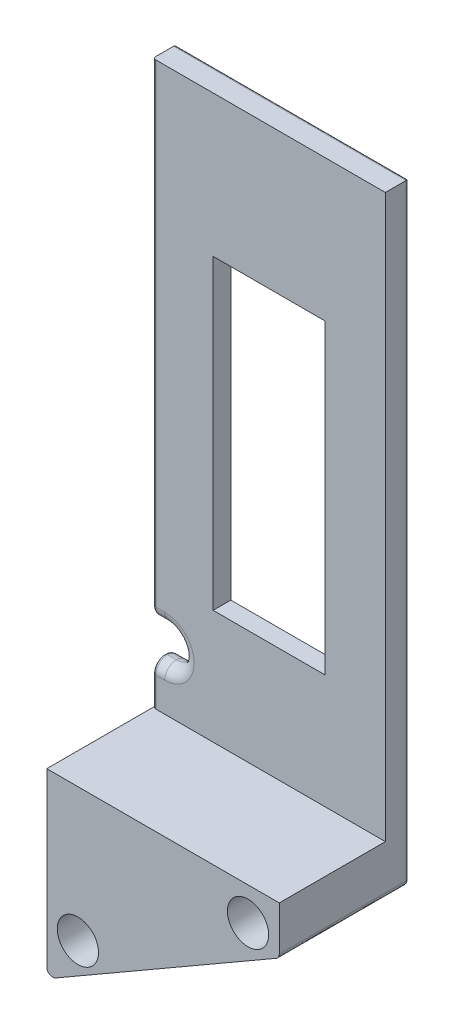
SolidWorks part; units mm, degrees
ref_plane "Front Plane" through (0, 0, 0) normal (0, 0, 1) x (1, 0, 0)
ref_plane "Top Plane" through (0, 0, 0) normal (0, 1, 0) x (1, 0, 0)
ref_plane "Right Plane" through (0, 0, 0) normal (1, 0, 0) x (0, 0, -1)
sketch "Model" plane through (0, 0, 0) normal (0, 0, 1) x (1, 0, 0)
  line L0 (-21.8431, 7.4481) -> (-8.6148, 30.3792)
  line L1 (-38.0636, 15.3297) -> (-23.771, 7.0696)
  line L2 (-75.3888, 20.2293) -> (-38.7189, 15.4592)
  line L3 (-86.2854, 34.8343) -> (-75.7419, 20.3766)
  line L4 (-29.1405, 92.9799) -> (-29.1405, 91.7303)
  line L5 (-8.8891, 91.2299) -> (-28.6402, 91.2299)
  line L6 (-8.3888, 90.7295) -> (-8.3888, 31.2555)
  line L7 (-86.6385, 34.9791) -> (-141.6396, 34.9791)
  line L8 (-142.1399, 90.7295) -> (-142.1399, 35.4795)
  line L9 (-104.6394, 91.2299) -> (-141.6396, 91.2299)
  line L10 (-104.139, 95.4793) -> (-104.139, 91.7303)
  line L11 (-85.6402, 95.9797) -> (-103.6387, 95.9797)
  line L12 (-85.1399, 97.7297) -> (-85.1399, 96.4801)
  line L13 (-67.6393, 98.2301) -> (-84.6395, 98.2301)
  line L14 (-67.1389, 96.4801) -> (-67.1389, 97.7297)
  line L15 (-48.6401, 95.9797) -> (-66.6385, 95.9797)
  line L16 (-48.1397, 93.9807) -> (-48.1397, 95.4793)
  line L17 (-29.6384, 93.4803) -> (-47.6393, 93.4803)
  line L18 (135.1563, 30.6526) -> (116.2359, 41.5721)
  line L19 (123.1828, 7.2669) -> (135.5373, 28.7222)
  line L20 (106.9623, 15.1485) -> (121.2549, 6.8884)
  line L21 (69.6371, 20.0481) -> (106.307, 15.278)
  line L22 (58.7405, 34.6531) -> (69.284, 20.1955)
  line L23 (115.8854, 92.7987) -> (115.8828, 42.2376)
  line L24 (58.3874, 34.7979) -> (3.3863, 34.7979)
  line L25 (2.886, 90.5483) -> (2.886, 35.2983)
  line L26 (40.3865, 91.0487) -> (3.3863, 91.0487)
  line L27 (40.8869, 95.2981) -> (40.8869, 91.5491)
  line L28 (59.3857, 95.7985) -> (41.3872, 95.7985)
  line L29 (59.886, 97.5485) -> (59.886, 96.2989)
  line L30 (77.3866, 98.0489) -> (60.3864, 98.0489)
  line L31 (77.887, 96.2989) -> (77.887, 97.5485)
  line L32 (96.3858, 95.7985) -> (78.3874, 95.7985)
  line L33 (96.8862, 93.7995) -> (96.8862, 95.2981)
  line L34 (115.3875, 93.2991) -> (97.3866, 93.2991)
  line L35 (20.1915, -96.2476) -> (6.9631, -73.3165)
  line L36 (36.4119, -88.366) -> (22.1193, -96.6261)
  line L37 (73.7371, -83.4663) -> (37.0672, -88.2365)
  line L38 (84.6337, -68.8614) -> (74.0902, -83.319)
  line L39 (27.4889, -10.7157) -> (27.4889, -11.9654)
  line L40 (7.2375, -12.4658) -> (26.9885, -12.4658)
  line L41 (6.7371, -12.9662) -> (6.7371, -72.4402)
  line L42 (84.9868, -68.7166) -> (139.9879, -68.7166)
  line L43 (140.4883, -12.9662) -> (140.4883, -68.2162)
  line L44 (102.9878, -12.4658) -> (139.9879, -12.4658)
  line L45 (102.4874, -8.2164) -> (102.4874, -11.9654)
  line L46 (83.9886, -7.716) -> (101.987, -7.716)
  line L47 (83.4882, -5.9659) -> (83.4882, -7.2156)
  line L48 (65.9876, -5.4656) -> (82.9878, -5.4656)
  line L49 (65.4872, -7.2156) -> (65.4872, -5.9659)
  line L50 (46.9884, -7.716) -> (64.9869, -7.716)
  line L51 (46.488, -9.715) -> (46.488, -8.2164)
  line L52 (27.9867, -10.2154) -> (45.9877, -10.2154)
  line L53 (-136.808, -73.043) -> (-117.8876, -62.1236)
  line L54 (-124.8344, -96.4288) -> (-137.189, -74.9734)
  line L55 (-108.614, -88.5472) -> (-122.9066, -96.8073)
  line L56 (-71.2888, -83.6475) -> (-107.9587, -88.4176)
  line L57 (-60.3922, -69.0425) -> (-70.9357, -83.5002)
  line L58 (-117.537, -10.8969) -> (-117.5345, -61.4581)
  line L59 (-60.0391, -68.8978) -> (-5.038, -68.8978)
  line L60 (-4.5376, -13.1474) -> (-4.5376, -68.3974)
  line L61 (-42.0381, -12.647) -> (-5.038, -12.647)
  line L62 (-42.5385, -8.3976) -> (-42.5385, -12.1466)
  line L63 (-61.0373, -7.8972) -> (-43.0389, -7.8972)
  line L64 (-61.5377, -6.1471) -> (-61.5377, -7.3968)
  line L65 (-79.0383, -5.6467) -> (-62.0381, -5.6467)
  line L66 (-79.5387, -7.3968) -> (-79.5387, -6.1471)
  line L67 (-98.0375, -7.8972) -> (-80.039, -7.8972)
  line L68 (-98.5378, -9.8962) -> (-98.5378, -8.3976)
  line L69 (-117.0392, -10.3965) -> (-99.0382, -10.3965)
  line L70 (138.9148, 92.1117) -> (138.9148, 33.3582)
  line L71 (138.1649, 32.9251) -> (119.446, 43.7282)
  line L72 (119.196, 44.1613) -> (119.196, 92.1092)
  line L73 (119.6959, 92.6092) -> (138.4148, 92.6117)
  line L74 (-140.5665, -11.584) -> (-140.5665, -70.3375)
  line L75 (-139.8166, -70.7706) -> (-121.0977, -59.9674)
  line L76 (-120.8476, -59.5344) -> (-120.8476, -11.5865)
  line L77 (-121.3476, -11.0865) -> (-140.0664, -11.084)
  line L78 (18.8966, 74.9256) -> (4.8966, 74.9256)
  line L79 (4.8966, 74.9256) -> (4.8966, 88.9256)
  line L80 (4.8966, 88.9256) -> (18.8966, 88.9256)
  line L81 (18.8966, 88.9256) -> (18.8966, 74.9256)
  line L82 (18.8966, 55.9256) -> (4.8966, 55.9256)
  line L83 (4.8966, 55.9256) -> (4.8966, 69.9256)
  line L84 (4.8966, 69.9256) -> (18.8966, 69.9256)
  line L85 (18.8966, 69.9256) -> (18.8966, 55.9256)
  line L86 (18.8966, 36.9256) -> (4.8966, 36.9256)
  line L87 (4.8966, 36.9256) -> (4.8966, 50.9256)
  line L88 (4.8966, 50.9256) -> (18.8966, 50.9256)
  line L89 (18.8966, 50.9256) -> (18.8966, 36.9256)
  line L90 (37.8948, 74.9262) -> (23.8948, 74.9262)
  line L91 (23.8948, 74.9262) -> (23.8948, 88.9262)
  line L92 (23.8948, 88.9262) -> (37.8948, 88.9262)
  line L93 (37.8948, 88.9262) -> (37.8948, 74.9262)
  line L94 (37.8948, 55.9262) -> (23.8948, 55.9262)
  line L95 (23.8948, 55.9262) -> (23.8948, 69.9262)
  line L96 (23.8948, 69.9262) -> (37.8948, 69.9262)
  line L97 (37.8948, 69.9262) -> (37.8948, 55.9262)
  line L98 (37.8948, 36.9262) -> (23.8948, 36.9262)
  line L99 (23.8948, 36.9262) -> (23.8948, 50.9262)
  line L100 (23.8948, 50.9262) -> (37.8948, 50.9262)
  line L101 (37.8948, 50.9262) -> (37.8948, 36.9262)
  line L102 (56.895, 79.671) -> (42.895, 79.671)
  line L103 (42.895, 79.671) -> (42.895, 93.671)
  line L104 (42.895, 93.671) -> (56.895, 93.671)
  line L105 (56.895, 93.671) -> (56.895, 79.671)
  line L106 (56.895, 60.6711) -> (42.895, 60.6711)
  line L107 (42.895, 60.6711) -> (42.895, 74.6711)
  line L108 (42.895, 74.6711) -> (56.895, 74.6711)
  line L109 (56.895, 74.6711) -> (56.895, 60.6711)
  line L110 (56.895, 41.6711) -> (42.895, 41.6711)
  line L111 (42.895, 41.6711) -> (42.895, 55.6711)
  line L112 (42.895, 55.6711) -> (56.895, 55.6711)
  line L113 (56.895, 55.6711) -> (56.895, 41.6711)
  line L114 (75.897, 82.0499) -> (61.897, 82.0499)
  line L115 (61.897, 82.0499) -> (61.897, 96.0499)
  line L116 (61.897, 96.0499) -> (75.897, 96.0499)
  line L117 (75.897, 96.0499) -> (75.897, 82.0499)
  line L118 (75.897, 63.0499) -> (61.897, 63.0499)
  line L119 (61.897, 63.0499) -> (61.897, 77.0499)
  line L120 (61.897, 77.0499) -> (75.897, 77.0499)
  line L121 (75.897, 77.0499) -> (75.897, 63.0499)
  line L122 (75.897, 44.0499) -> (61.897, 44.0499)
  line L123 (61.897, 44.0499) -> (61.897, 58.0499)
  line L124 (61.897, 58.0499) -> (75.897, 58.0499)
  line L125 (75.897, 58.0499) -> (75.897, 44.0499)
  line L126 (94.8982, 79.6753) -> (80.8982, 79.6753)
  line L127 (80.8982, 79.6753) -> (80.8982, 93.6753)
  line L128 (80.8982, 93.6753) -> (94.8982, 93.6753)
  line L129 (94.8982, 93.6753) -> (94.8982, 79.6753)
  line L130 (94.8982, 60.6753) -> (80.8982, 60.6753)
  line L131 (80.8982, 60.6753) -> (80.8982, 74.6753)
  line L132 (80.8982, 74.6753) -> (94.8982, 74.6753)
  line L133 (94.8982, 74.6753) -> (94.8982, 60.6753)
  line L134 (94.8982, 41.6753) -> (80.8982, 41.6753)
  line L135 (80.8982, 41.6753) -> (80.8982, 55.6753)
  line L136 (80.8982, 55.6753) -> (94.8982, 55.6753)
  line L137 (94.8982, 55.6753) -> (94.8982, 41.6753)
  line L138 (113.9, 77.2905) -> (99.9, 77.2905)
  line L139 (99.9, 77.2905) -> (99.9, 91.2905)
  line L140 (99.9, 91.2905) -> (113.9, 91.2905)
  line L141 (113.9, 91.2905) -> (113.9, 77.2905)
  line L142 (113.9, 58.2905) -> (99.9, 58.2905)
  line L143 (99.9, 58.2905) -> (99.9, 72.2905)
  line L144 (99.9, 72.2905) -> (113.9, 72.2905)
  line L145 (113.9, 72.2905) -> (113.9, 58.2905)
  line L146 (113.9, 39.2905) -> (99.9, 39.2905)
  line L147 (99.9, 39.2905) -> (99.9, 53.2905)
  line L148 (99.9, 53.2905) -> (113.9, 53.2905)
  line L149 (113.9, 53.2905) -> (113.9, 39.2905)
  line L150 (85.4166, 22.0174) -> (71.4166, 22.0174)
  line L151 (71.4166, 22.0174) -> (71.4166, 36.0174)
  line L152 (71.4166, 36.0174) -> (85.4166, 36.0174)
  line L153 (85.4166, 36.0174) -> (85.4166, 22.0174)
  line L154 (104.3289, 17.734) -> (90.806, 21.3575)
  line L155 (90.806, 21.3575) -> (94.4294, 34.8805)
  line L156 (94.4294, 34.8805) -> (107.9524, 31.257)
  line L157 (107.9524, 31.257) -> (104.3289, 17.734)
  line L158 (124.1994, 13.0049) -> (112.075, 20.0049)
  line L159 (112.075, 20.0049) -> (119.075, 32.1293)
  line L160 (119.075, 32.1293) -> (131.1994, 25.1293)
  line L161 (131.1994, 25.1293) -> (124.1994, 13.0049)
  line L162 (-20.5483, -28.7701) -> (-6.5483, -28.7701)
  line L163 (-6.5483, -28.7701) -> (-6.5483, -14.7701)
  line L164 (-6.5483, -14.7701) -> (-20.5483, -14.7701)
  line L165 (-20.5483, -14.7701) -> (-20.5483, -28.7701)
  line L166 (-20.5483, -47.7701) -> (-6.5483, -47.7701)
  line L167 (-6.5483, -47.7701) -> (-6.5483, -33.7701)
  line L168 (-6.5483, -33.7701) -> (-20.5483, -33.7701)
  line L169 (-20.5483, -33.7701) -> (-20.5483, -47.7701)
  line L170 (-20.5483, -66.7701) -> (-6.5483, -66.7701)
  line L171 (-6.5483, -66.7701) -> (-6.5483, -52.7701)
  line L172 (-6.5483, -52.7701) -> (-20.5483, -52.7701)
  line L173 (-20.5483, -52.7701) -> (-20.5483, -66.7701)
  line L174 (-39.5464, -28.7694) -> (-25.5464, -28.7694)
  line L175 (-25.5464, -28.7694) -> (-25.5464, -14.7694)
  line L176 (-25.5464, -14.7694) -> (-39.5464, -14.7694)
  line L177 (-39.5464, -14.7694) -> (-39.5464, -28.7694)
  line L178 (-39.5464, -47.7694) -> (-25.5464, -47.7694)
  line L179 (-25.5464, -47.7694) -> (-25.5464, -33.7694)
  line L180 (-25.5464, -33.7694) -> (-39.5464, -33.7694)
  line L181 (-39.5464, -33.7694) -> (-39.5464, -47.7694)
  line L182 (-39.5464, -66.7694) -> (-25.5464, -66.7694)
  line L183 (-25.5464, -66.7694) -> (-25.5464, -52.7694)
  line L184 (-25.5464, -52.7694) -> (-39.5464, -52.7694)
  line L185 (-39.5464, -52.7694) -> (-39.5464, -66.7694)
  line L186 (-58.5467, -24.0246) -> (-44.5467, -24.0246)
  line L187 (-44.5467, -24.0246) -> (-44.5467, -10.0246)
  line L188 (-44.5467, -10.0246) -> (-58.5467, -10.0246)
  line L189 (-58.5467, -10.0246) -> (-58.5467, -24.0246)
  line L190 (-58.5467, -43.0246) -> (-44.5467, -43.0246)
  line L191 (-44.5467, -43.0246) -> (-44.5467, -29.0246)
  line L192 (-44.5467, -29.0246) -> (-58.5467, -29.0246)
  line L193 (-58.5467, -29.0246) -> (-58.5467, -43.0246)
  line L194 (-58.5467, -62.0246) -> (-44.5467, -62.0246)
  line L195 (-44.5467, -62.0246) -> (-44.5467, -48.0246)
  line L196 (-44.5467, -48.0246) -> (-58.5467, -48.0246)
  line L197 (-58.5467, -48.0246) -> (-58.5467, -62.0246)
  line L198 (-77.5486, -21.6458) -> (-63.5486, -21.6458)
  line L199 (-63.5486, -21.6458) -> (-63.5486, -7.6458)
  line L200 (-63.5486, -7.6458) -> (-77.5486, -7.6458)
  line L201 (-77.5486, -7.6458) -> (-77.5486, -21.6458)
  line L202 (-77.5486, -40.6458) -> (-63.5486, -40.6458)
  line L203 (-63.5486, -40.6458) -> (-63.5486, -26.6458)
  line L204 (-63.5486, -26.6458) -> (-77.5486, -26.6458)
  line L205 (-77.5486, -26.6458) -> (-77.5486, -40.6458)
  line L206 (-77.5486, -59.6458) -> (-63.5486, -59.6458)
  line L207 (-63.5486, -59.6458) -> (-63.5486, -45.6458)
  line L208 (-63.5486, -45.6458) -> (-77.5486, -45.6458)
  line L209 (-77.5486, -45.6458) -> (-77.5486, -59.6458)
  line L210 (-96.5499, -24.0204) -> (-82.5499, -24.0204)
  line L211 (-82.5499, -24.0204) -> (-82.5499, -10.0204)
  line L212 (-82.5499, -10.0204) -> (-96.5499, -10.0204)
  line L213 (-96.5499, -10.0204) -> (-96.5499, -24.0204)
  line L214 (-96.5499, -43.0203) -> (-82.5499, -43.0203)
  line L215 (-82.5499, -43.0203) -> (-82.5499, -29.0203)
  line L216 (-82.5499, -29.0203) -> (-96.5499, -29.0203)
  line L217 (-96.5499, -29.0203) -> (-96.5499, -43.0203)
  line L218 (-96.5499, -62.0203) -> (-82.5499, -62.0203)
  line L219 (-82.5499, -62.0203) -> (-82.5499, -48.0203)
  line L220 (-82.5499, -48.0203) -> (-96.5499, -48.0203)
  line L221 (-96.5499, -48.0203) -> (-96.5499, -62.0203)
  line L222 (-115.5516, -26.4052) -> (-101.5516, -26.4052)
  line L223 (-101.5516, -26.4052) -> (-101.5516, -12.4052)
  line L224 (-101.5516, -12.4052) -> (-115.5516, -12.4052)
  line L225 (-115.5516, -12.4052) -> (-115.5516, -26.4052)
  line L226 (-115.5516, -45.4052) -> (-101.5516, -45.4052)
  line L227 (-101.5516, -45.4052) -> (-101.5516, -31.4052)
  line L228 (-101.5516, -31.4052) -> (-115.5516, -31.4052)
  line L229 (-115.5516, -31.4052) -> (-115.5516, -45.4052)
  line L230 (-115.5516, -64.4052) -> (-101.5516, -64.4052)
  line L231 (-101.5516, -64.4052) -> (-101.5516, -50.4052)
  line L232 (-101.5516, -50.4052) -> (-115.5516, -50.4052)
  line L233 (-115.5516, -50.4052) -> (-115.5516, -64.4052)
  line L234 (-87.0683, -81.6783) -> (-73.0683, -81.6783)
  line L235 (-73.0683, -81.6783) -> (-73.0683, -67.6783)
  line L236 (-73.0683, -67.6783) -> (-87.0683, -67.6783)
  line L237 (-87.0683, -67.6783) -> (-87.0683, -81.6783)
  line L238 (-105.9806, -85.9616) -> (-92.4576, -82.3382)
  line L239 (-92.4576, -82.3382) -> (-96.0811, -68.8152)
  line L240 (-96.0811, -68.8152) -> (-109.6041, -72.4387)
  line L241 (-109.6041, -72.4387) -> (-105.9806, -85.9616)
  line L242 (-125.851, -90.6908) -> (-113.7267, -83.6908)
  line L243 (-113.7267, -83.6908) -> (-120.7267, -71.5664)
  line L244 (-120.7267, -71.5664) -> (-132.851, -78.5664)
  line L245 (-132.851, -78.5664) -> (-125.851, -90.6908)
  spline S0 degree 3 poles (-8.6153, 30.3807) (-8.4626, 30.6458) (-8.3842, 30.9472) (-8.3882, 31.2532) knots 0 0 0 0 1 1 1 1
  spline S1 degree 3 poles (-21.8439, 7.4422) (-21.8429, 7.4437) (-21.8419, 7.4453) (-21.8408, 7.4468) knots 1 1 1 1 2 2 2 2
  spline S2 degree 3 poles (-23.769, 7.0673) (-23.1339, 6.6392) (-22.272, 6.8071) (-21.8439, 7.4422) knots 0 0 0 0 1 1 1 1
  spline S3 degree 3 poles (-38.063, 15.3284) (-38.2765, 15.3928) (-38.4957, 15.4362) (-38.7176, 15.4579) knots 0 0 0 0 1 1 1 1
  spline S4 degree 3 poles (-75.7416, 20.3746) (-75.6478, 20.2809) (-75.5206, 20.2283) (-75.3881, 20.2283) knots 0 0 0 0 1 1 1 1
  spline S5 degree 3 poles (-29.1383, 92.9782) (-29.1382, 93.2543) (-29.362, 93.4782) (-29.6381, 93.4783) knots 0 0 0 0 1 1 1 1
  spline S6 degree 3 poles (-29.1383, 91.7282) (-29.1383, 91.4521) (-28.9145, 91.2282) (-28.6384, 91.2281) (-28.6383, 91.2281) (-28.6382, 91.2281) (-28.6381, 91.2281) knots 0 0 0 0 1 1 1 2 2 2 2
  spline S7 degree 3 poles (-86.2846, 34.8318) (-86.3784, 34.9256) (-86.5056, 34.9783) (-86.6385, 34.9791) knots 0 0 0 0 1 1 1 1
  spline S8 degree 3 poles (-142.1382, 35.4782) (-142.1381, 35.2021) (-141.9142, 34.9783) (-141.6381, 34.9783) knots 0 0 0 0 1 1 1 1
  spline S9 degree 3 poles (-141.638, 91.2281) (-141.9142, 91.2282) (-142.1381, 91.0044) (-142.1382, 90.7282) knots 0 0 0 0 1 1 1 1
  spline S10 degree 3 poles (-104.6382, 91.2281) (-104.362, 91.228) (-104.1381, 91.4518) (-104.138, 91.728) (-104.138, 91.7281) (-104.138, 91.7281) (-104.138, 91.7282) knots 0 0 0 0 1 1 1 2 2 2 2
  spline S11 degree 3 poles (-103.6382, 95.9781) (-103.9142, 95.9781) (-104.138, 95.7543) (-104.138, 95.4783) knots 0 0 0 0 1 1 1 1
  spline S12 degree 3 poles (-85.6382, 95.9781) (-85.3621, 95.9781) (-85.1382, 96.2019) (-85.1381, 96.478) (-85.1381, 96.4781) (-85.1381, 96.4782) (-85.1381, 96.4783) knots 0 0 0 0 1 1 1 2 2 2 2
  spline S13 degree 3 poles (-84.6382, 98.2283) (-84.9144, 98.2283) (-85.1382, 98.0044) (-85.1381, 97.7282) knots 0 0 0 0 1 1 1 1
  spline S14 degree 3 poles (-67.1381, 97.7282) (-67.1381, 98.0043) (-67.3619, 98.2283) (-67.638, 98.2283) knots 0 0 0 0 2 2 2 2
  spline S15 degree 3 poles (-67.1381, 96.4783) (-67.1382, 96.2021) (-66.9144, 95.9782) (-66.6383, 95.9781) (-66.6382, 95.9781) (-66.6381, 95.9781) (-66.638, 95.9781) knots 0 0 0 0 1 1 1 2 2 2 2
  spline S16 degree 3 poles (-48.1382, 95.4783) (-48.1383, 95.7543) (-48.362, 95.9781) (-48.6381, 95.9781) knots 0 0 0 0 1 1 1 1
  spline S17 degree 3 poles (-48.1382, 93.9782) (-48.1381, 93.702) (-47.9142, 93.4782) (-47.6381, 93.4783) knots 0 0 0 0 1 1 1 1
  spline S18 degree 3 poles (-8.3882, 90.7282) (-8.3883, 91.0043) (-8.6121, 91.228) (-8.8881, 91.2281) knots 0 0 0 0 1 1 1 1
  spline S19 degree 3 poles (115.8851, 42.2368) (115.8929, 41.9725) (116.0232, 41.7268) (116.2377, 41.5721) knots 0 0 0 0 1 1 1 1
  spline S20 degree 3 poles (135.163, 30.647) (135.1614, 30.648) (135.1599, 30.6491) (135.1583, 30.6501) knots 1 1 1 1 2 2 2 2
  spline S21 degree 3 poles (135.5373, 28.7222) (135.9659, 29.3571) (135.7981, 30.2189) (135.163, 30.647) knots 0 0 0 0 1 1 1 1
  spline S22 degree 3 poles (123.182, 7.261) (123.183, 7.2625) (123.184, 7.2641) (123.1851, 7.2656) knots 1 1 1 1 2 2 2 2
  spline S23 degree 3 poles (121.2569, 6.8861) (121.892, 6.4581) (122.7539, 6.6259) (123.182, 7.261) knots 0 0 0 0 1 1 1 1
  spline S24 degree 3 poles (106.9629, 15.1472) (106.7494, 15.2117) (106.5302, 15.255) (106.3083, 15.2768) knots 0 0 0 0 1 1 1 1
  spline S25 degree 3 poles (69.2843, 20.1934) (69.3781, 20.0997) (69.5053, 20.0471) (69.6378, 20.0471) knots 0 0 0 0 1 1 1 1
  spline S26 degree 3 poles (115.8876, 92.797) (115.8877, 93.0731) (115.6639, 93.297) (115.3878, 93.2971) knots 0 0 0 0 1 1 1 1
  spline S27 degree 3 poles (58.7413, 34.6506) (58.6475, 34.7444) (58.5203, 34.7971) (58.3874, 34.7979) knots 0 0 0 0 1 1 1 1
  spline S28 degree 3 poles (2.8877, 35.297) (2.8878, 35.0209) (3.1117, 34.7971) (3.3878, 34.7971) knots 0 0 0 0 1 1 1 1
  spline S29 degree 3 poles (3.3879, 91.0469) (3.1117, 91.047) (2.8878, 90.8232) (2.8877, 90.547) knots 0 0 0 0 1 1 1 1
  spline S30 degree 3 poles (40.3877, 91.0469) (40.6639, 91.0468) (40.8878, 91.2706) (40.8879, 91.5468) (40.8879, 91.5469) (40.8879, 91.5469) (40.8879, 91.547) knots 0 0 0 0 1 1 1 2 2 2 2
  spline S31 degree 3 poles (41.3877, 95.797) (41.1117, 95.7969) (40.8879, 95.5731) (40.8879, 95.2971) knots 0 0 0 0 1 1 1 1
  spline S32 degree 3 poles (59.3877, 95.797) (59.6638, 95.7969) (59.8877, 96.0207) (59.8878, 96.2968) (59.8878, 96.2969) (59.8878, 96.297) (59.8878, 96.2971) knots 0 0 0 0 1 1 1 2 2 2 2
  spline S33 degree 3 poles (60.3877, 98.0471) (60.1115, 98.0471) (59.8877, 97.8232) (59.8878, 97.547) knots 0 0 0 0 1 1 1 1
  spline S34 degree 3 poles (77.8878, 97.547) (77.8878, 97.8232) (77.664, 98.0471) (77.3879, 98.0471) knots 0 0 0 0 2 2 2 2
  spline S35 degree 3 poles (77.8878, 96.2971) (77.8877, 96.0209) (78.1115, 95.797) (78.3876, 95.797) (78.3877, 95.797) (78.3878, 95.797) (78.3879, 95.797) knots 0 0 0 0 1 1 1 2 2 2 2
  spline S36 degree 3 poles (96.8877, 95.2971) (96.8876, 95.5731) (96.6639, 95.7969) (96.3878, 95.797) knots 0 0 0 0 1 1 1 1
  spline S37 degree 3 poles (96.8877, 93.797) (96.8878, 93.5208) (97.1117, 93.297) (97.3878, 93.2971) knots 0 0 0 0 1 1 1 1
  spline S38 degree 3 poles (6.9637, -73.315) (6.8109, -73.0499) (6.7325, -72.7484) (6.7366, -72.4425) knots 0 0 0 0 1 1 1 1
  spline S39 degree 3 poles (20.1923, -96.2535) (20.1912, -96.252) (20.1902, -96.2504) (20.1892, -96.2489) knots 1 1 1 1 2 2 2 2
  spline S40 degree 3 poles (22.1173, -96.6284) (21.4822, -97.0564) (20.6203, -96.8886) (20.1923, -96.2535) knots 0 0 0 0 1 1 1 1
  spline S41 degree 3 poles (36.4114, -88.3673) (36.6248, -88.3028) (36.844, -88.2594) (37.0659, -88.2377) knots 0 0 0 0 1 1 1 1
  spline S42 degree 3 poles (74.0899, -83.3211) (73.9962, -83.4148) (73.869, -83.4674) (73.7364, -83.4674) knots 0 0 0 0 1 1 1 1
  spline S43 degree 3 poles (27.4866, -10.7175) (27.4865, -10.4414) (27.7103, -10.2175) (27.9865, -10.2174) knots 0 0 0 0 1 1 1 1
  spline S44 degree 3 poles (27.4866, -11.9674) (27.4866, -12.2436) (27.2628, -12.4675) (26.9867, -12.4676) (26.9866, -12.4676) (26.9865, -12.4676) (26.9865, -12.4676) knots 0 0 0 0 1 1 1 2 2 2 2
  spline S45 degree 3 poles (84.633, -68.8639) (84.7267, -68.7701) (84.8539, -68.7174) (84.9868, -68.7166) knots 0 0 0 0 1 1 1 1
  spline S46 degree 3 poles (140.4865, -68.2175) (140.4864, -68.4936) (140.2625, -68.7174) (139.9864, -68.7173) knots 0 0 0 0 1 1 1 1
  spline S47 degree 3 poles (139.9864, -12.4676) (140.2625, -12.4675) (140.4864, -12.6913) (140.4865, -12.9674) knots 0 0 0 0 1 1 1 1
  spline S48 degree 3 poles (102.9865, -12.4676) (102.7103, -12.4676) (102.4864, -12.2438) (102.4864, -11.9677) (102.4864, -11.9676) (102.4864, -11.9675) (102.4864, -11.9674) knots 0 0 0 0 1 1 1 2 2 2 2
  spline S49 degree 3 poles (101.9865, -7.7175) (102.2625, -7.7176) (102.4863, -7.9413) (102.4864, -8.2174) knots 0 0 0 0 1 1 1 1
  spline S50 degree 3 poles (83.9865, -7.7175) (83.7104, -7.7176) (83.4865, -7.4938) (83.4864, -7.2176) (83.4864, -7.2176) (83.4864, -7.2175) (83.4864, -7.2174) knots 0 0 0 0 1 1 1 2 2 2 2
  spline S51 degree 3 poles (82.9865, -5.4673) (83.2627, -5.4674) (83.4865, -5.6913) (83.4864, -5.9675) knots 0 0 0 0 1 1 1 1
  spline S52 degree 3 poles (65.4865, -5.9675) (65.4864, -5.6913) (65.7102, -5.4674) (65.9863, -5.4673) knots 0 0 0 0 2 2 2 2
  spline S53 degree 3 poles (65.4865, -7.2174) (65.4865, -7.4935) (65.2627, -7.7174) (64.9866, -7.7175) (64.9865, -7.7175) (64.9864, -7.7175) (64.9863, -7.7175) knots 0 0 0 0 1 1 1 2 2 2 2
  spline S54 degree 3 poles (46.4865, -8.2174) (46.4866, -7.9413) (46.7103, -7.7176) (46.9864, -7.7175) knots 0 0 0 0 1 1 1 1
  spline S55 degree 3 poles (46.4865, -9.7175) (46.4865, -9.9937) (46.2625, -10.2175) (45.9864, -10.2174) knots 0 0 0 0 1 1 1 1
  spline S56 degree 3 poles (6.7366, -12.9674) (6.7366, -12.6914) (6.9604, -12.4676) (7.2365, -12.4676) knots 0 0 0 0 1 1 1 1
  spline S57 degree 3 poles (-117.5368, -61.4589) (-117.5446, -61.7232) (-117.6748, -61.9689) (-117.8893, -62.1236) knots 0 0 0 0 1 1 1 1
  spline S58 degree 3 poles (-136.8146, -73.0487) (-136.8131, -73.0476) (-136.8116, -73.0466) (-136.81, -73.0456) knots 1 1 1 1 2 2 2 2
  spline S59 degree 3 poles (-137.189, -74.9734) (-137.6176, -74.3386) (-137.4497, -73.4767) (-136.8146, -73.0487) knots 0 0 0 0 1 1 1 1
  spline S60 degree 3 poles (-124.8336, -96.4347) (-124.8347, -96.4331) (-124.8357, -96.4316) (-124.8367, -96.4301) knots 1 1 1 1 2 2 2 2
  spline S61 degree 3 poles (-122.9086, -96.8095) (-123.5437, -97.2376) (-124.4056, -97.0698) (-124.8336, -96.4347) knots 0 0 0 0 1 1 1 1
  spline S62 degree 3 poles (-108.6145, -88.5485) (-108.4011, -88.484) (-108.1819, -88.4406) (-107.96, -88.4189) knots 0 0 0 0 1 1 1 1
  spline S63 degree 3 poles (-70.936, -83.5022) (-71.0297, -83.596) (-71.1569, -83.6486) (-71.2895, -83.6485) knots 0 0 0 0 1 1 1 1
  spline S64 degree 3 poles (-117.5393, -10.8987) (-117.5394, -10.6226) (-117.3156, -10.3987) (-117.0394, -10.3986) knots 0 0 0 0 1 1 1 1
  spline S65 degree 3 poles (-60.3929, -69.0451) (-60.2992, -68.9513) (-60.172, -68.8986) (-60.0391, -68.8978) knots 0 0 0 0 1 1 1 1
  spline S66 degree 3 poles (-4.5394, -68.3987) (-4.5395, -68.6748) (-4.7634, -68.8986) (-5.0395, -68.8985) knots 0 0 0 0 1 1 1 1
  spline S67 degree 3 poles (-5.0395, -12.6488) (-4.7634, -12.6487) (-4.5395, -12.8725) (-4.5394, -13.1486) knots 0 0 0 0 1 1 1 1
  spline S68 degree 3 poles (-42.0394, -12.6488) (-42.3156, -12.6488) (-42.5395, -12.425) (-42.5395, -12.1489) (-42.5395, -12.1488) (-42.5395, -12.1487) (-42.5395, -12.1486) knots 0 0 0 0 1 1 1 2 2 2 2
  spline S69 degree 3 poles (-43.0394, -7.8987) (-42.7634, -7.8988) (-42.5396, -8.1225) (-42.5395, -8.3986) knots 0 0 0 0 1 1 1 1
  spline S70 degree 3 poles (-61.0394, -7.8987) (-61.3155, -7.8988) (-61.5394, -7.675) (-61.5395, -7.3988) (-61.5395, -7.3988) (-61.5395, -7.3987) (-61.5395, -7.3986) knots 0 0 0 0 1 1 1 2 2 2 2
  spline S71 degree 3 poles (-62.0394, -5.6485) (-61.7632, -5.6486) (-61.5394, -5.8725) (-61.5395, -6.1486) knots 0 0 0 0 1 1 1 1
  spline S72 degree 3 poles (-79.5394, -6.1486) (-79.5395, -5.8725) (-79.3157, -5.6486) (-79.0396, -5.6485) knots 0 0 0 0 2 2 2 2
  spline S73 degree 3 poles (-79.5394, -7.3986) (-79.5394, -7.6747) (-79.7632, -7.8986) (-80.0393, -7.8987) (-80.0394, -7.8987) (-80.0395, -7.8987) (-80.0396, -7.8987) knots 0 0 0 0 1 1 1 2 2 2 2
  spline S74 degree 3 poles (-98.5394, -8.3986) (-98.5393, -8.1225) (-98.3156, -7.8988) (-98.0395, -7.8987) knots 0 0 0 0 1 1 1 1
  spline S75 degree 3 poles (-98.5394, -9.8987) (-98.5394, -10.1748) (-98.7634, -10.3986) (-99.0395, -10.3986) knots 0 0 0 0 1 1 1 1
  spline S76 degree 3 poles (-123.6381, 52.6314) (-124.2456, 52.6314) (-124.7381, 53.1239) (-124.7381, 53.7314) (-124.7381, 54.3389) (-124.2456, 54.8314) (-123.6381, 54.8314) knots 2 2 2 2 3 3 3 4 4 4 4
  spline S77 degree 3 poles (-123.6381, 54.8314) (-123.0306, 54.8314) (-122.5381, 54.3389) (-122.5381, 53.7314) (-122.5381, 53.1239) (-123.0306, 52.6314) (-123.6381, 52.6314) knots 0 0 0 0 1 1 1 2 2 2 2
  spline S78 degree 3 poles (-123.6381, 71.3814) (-124.2456, 71.3814) (-124.7381, 71.8739) (-124.7381, 72.4814) (-124.7381, 73.0889) (-124.2456, 73.5814) (-123.6381, 73.5814) knots 2 2 2 2 3 3 3 4 4 4 4
  spline S79 degree 3 poles (-123.6381, 73.5814) (-123.0306, 73.5814) (-122.5381, 73.0889) (-122.5381, 72.4814) (-122.5381, 71.8739) (-123.0306, 71.3814) (-123.6381, 71.3814) knots 0 0 0 0 1 1 1 2 2 2 2
  spline S80 degree 3 poles (-47.6381, 75.1312) (-48.2456, 75.1312) (-48.7381, 75.6237) (-48.7381, 76.2312) (-48.7381, 76.8387) (-48.2456, 77.3312) (-47.6381, 77.3312) knots 2 2 2 2 3 3 3 4 4 4 4
  spline S81 degree 3 poles (-47.6381, 77.3312) (-47.0306, 77.3312) (-46.5381, 76.8387) (-46.5381, 76.2312) (-46.5381, 75.6237) (-47.0306, 75.1312) (-47.6381, 75.1312) knots 0 0 0 0 1 1 1 2 2 2 2
  spline S82 degree 3 poles (-80.388, 35.3813) (-80.9956, 35.3813) (-81.488, 35.8738) (-81.488, 36.4813) (-81.488, 37.0888) (-80.9956, 37.5813) (-80.388, 37.5813) knots 2 2 2 2 3 3 3 4 4 4 4
  spline S83 degree 3 poles (-80.388, 37.5813) (-79.7805, 37.5813) (-79.288, 37.0888) (-79.288, 36.4813) (-79.288, 35.8738) (-79.7805, 35.3813) (-80.388, 35.3813) knots 0 0 0 0 1 1 1 2 2 2 2
  spline S84 degree 3 poles (-33.8881, 27.6312) (-34.4956, 27.6312) (-34.9881, 28.1237) (-34.9881, 28.7312) (-34.9881, 29.3388) (-34.4956, 29.8312) (-33.8881, 29.8312) knots 2 2 2 2 3 3 3 4 4 4 4
  spline S85 degree 3 poles (-33.8881, 29.8312) (-33.2805, 29.8312) (-32.7881, 29.3388) (-32.7881, 28.7312) (-32.7881, 28.1237) (-33.2805, 27.6312) (-33.8881, 27.6312) knots 0 0 0 0 1 1 1 2 2 2 2
  spline S86 degree 3 poles (21.3878, 52.4502) (20.7803, 52.4502) (20.2878, 52.9427) (20.2878, 53.5502) (20.2878, 54.1578) (20.7803, 54.6502) (21.3878, 54.6502) knots 2 2 2 2 3 3 3 4 4 4 4
  spline S87 degree 3 poles (21.3878, 54.6502) (21.9953, 54.6502) (22.4878, 54.1578) (22.4878, 53.5502) (22.4878, 52.9427) (21.9953, 52.4502) (21.3878, 52.4502) knots 0 0 0 0 1 1 1 2 2 2 2
  spline S88 degree 3 poles (97.3878, 74.95) (96.7803, 74.95) (96.2878, 75.4425) (96.2878, 76.05) (96.2878, 76.6575) (96.7803, 77.15) (97.3878, 77.15) knots 2 2 2 2 3 3 3 4 4 4 4
  spline S89 degree 3 poles (97.3878, 77.15) (97.9953, 77.15) (98.4878, 76.6575) (98.4878, 76.05) (98.4878, 75.4425) (97.9953, 74.95) (97.3878, 74.95) knots 0 0 0 0 1 1 1 2 2 2 2
  spline S90 degree 3 poles (64.6379, 35.2001) (64.0303, 35.2001) (63.5379, 35.6926) (63.5379, 36.3001) (63.5379, 36.9076) (64.0303, 37.4001) (64.6379, 37.4001) knots 2 2 2 2 3 3 3 4 4 4 4
  spline S91 degree 3 poles (64.6379, 37.4001) (65.2454, 37.4001) (65.7379, 36.9076) (65.7379, 36.3001) (65.7379, 35.6926) (65.2454, 35.2001) (64.6379, 35.2001) knots 0 0 0 0 1 1 1 2 2 2 2
  spline S92 degree 3 poles (111.1378, 27.4501) (110.5303, 27.4501) (110.0378, 27.9425) (110.0378, 28.5501) (110.0378, 29.1576) (110.5303, 29.65) (111.1378, 29.65) knots 2 2 2 2 3 3 3 4 4 4 4
  spline S93 degree 3 poles (111.1378, 29.65) (111.7454, 29.65) (112.2378, 29.1576) (112.2378, 28.5501) (112.2378, 27.9425) (111.7454, 27.4501) (111.1378, 27.4501) knots 0 0 0 0 1 1 1 2 2 2 2
  spline S94 degree 3 poles (121.9864, -51.0642) (122.5939, -51.0642) (123.0864, -50.5718) (123.0864, -49.9642) (123.0864, -49.3567) (122.5939, -48.8642) (121.9864, -48.8642) knots 2 2 2 2 3 3 3 4 4 4 4
  spline S95 degree 3 poles (121.9864, -48.8642) (121.3789, -48.8642) (120.8864, -49.3567) (120.8864, -49.9642) (120.8864, -50.5718) (121.3789, -51.0642) (121.9864, -51.0642) knots 0 0 0 0 1 1 1 2 2 2 2
  spline S96 degree 3 poles (121.9864, -32.3142) (122.5939, -32.3142) (123.0864, -31.8218) (123.0864, -31.2142) (123.0864, -30.6067) (122.5939, -30.1142) (121.9864, -30.1142) knots 2 2 2 2 3 3 3 4 4 4 4
  spline S97 degree 3 poles (121.9864, -30.1142) (121.3789, -30.1142) (120.8864, -30.6067) (120.8864, -31.2142) (120.8864, -31.8218) (121.3789, -32.3142) (121.9864, -32.3142) knots 0 0 0 0 1 1 1 2 2 2 2
  spline S98 degree 3 poles (45.9864, -28.5644) (46.5939, -28.5644) (47.0864, -28.072) (47.0864, -27.4644) (47.0864, -26.8569) (46.5939, -26.3644) (45.9864, -26.3644) knots 2 2 2 2 3 3 3 4 4 4 4
  spline S99 degree 3 poles (45.9864, -26.3644) (45.3789, -26.3644) (44.8864, -26.8569) (44.8864, -27.4644) (44.8864, -28.072) (45.3789, -28.5644) (45.9864, -28.5644) knots 0 0 0 0 1 1 1 2 2 2 2
  spline S100 degree 3 poles (78.7364, -68.3144) (79.3439, -68.3144) (79.8364, -67.8219) (79.8364, -67.2144) (79.8364, -66.6069) (79.3439, -66.1144) (78.7364, -66.1144) knots 2 2 2 2 3 3 3 4 4 4 4
  spline S101 degree 3 poles (78.7364, -66.1144) (78.1288, -66.1144) (77.6364, -66.6069) (77.6364, -67.2144) (77.6364, -67.8219) (78.1288, -68.3144) (78.7364, -68.3144) knots 0 0 0 0 1 1 1 2 2 2 2
  spline S102 degree 3 poles (32.2364, -76.0644) (32.8439, -76.0644) (33.3364, -75.5719) (33.3364, -74.9644) (33.3364, -74.3569) (32.8439, -73.8644) (32.2364, -73.8644) knots 2 2 2 2 3 3 3 4 4 4 4
  spline S103 degree 3 poles (32.2364, -73.8644) (31.6289, -73.8644) (31.1364, -74.3569) (31.1364, -74.9644) (31.1364, -75.5719) (31.6289, -76.0644) (32.2364, -76.0644) knots 0 0 0 0 1 1 1 2 2 2 2
  spline S104 degree 3 poles (-23.0395, -51.2454) (-22.432, -51.2454) (-21.9395, -50.7529) (-21.9395, -50.1454) (-21.9395, -49.5379) (-22.432, -49.0454) (-23.0395, -49.0454) knots 2 2 2 2 3 3 3 4 4 4 4
  spline S105 degree 3 poles (-23.0395, -49.0454) (-23.647, -49.0454) (-24.1395, -49.5379) (-24.1395, -50.1454) (-24.1395, -50.7529) (-23.647, -51.2454) (-23.0395, -51.2454) knots 0 0 0 0 1 1 1 2 2 2 2
  spline S106 degree 3 poles (-99.0395, -28.7456) (-98.432, -28.7456) (-97.9395, -28.2531) (-97.9395, -27.6456) (-97.9395, -27.0381) (-98.432, -26.5456) (-99.0395, -26.5456) knots 2 2 2 2 3 3 3 4 4 4 4
  spline S107 degree 3 poles (-99.0395, -26.5456) (-99.647, -26.5456) (-100.1395, -27.0381) (-100.1395, -27.6456) (-100.1395, -28.2531) (-99.647, -28.7456) (-99.0395, -28.7456) knots 0 0 0 0 1 1 1 2 2 2 2
  spline S108 degree 3 poles (-66.2895, -68.4956) (-65.682, -68.4956) (-65.1895, -68.0031) (-65.1895, -67.3956) (-65.1895, -66.7881) (-65.682, -66.2956) (-66.2895, -66.2956) knots 2 2 2 2 3 3 3 4 4 4 4
  spline S109 degree 3 poles (-66.2895, -66.2956) (-66.8971, -66.2956) (-67.3895, -66.7881) (-67.3895, -67.3956) (-67.3895, -68.0031) (-66.8971, -68.4956) (-66.2895, -68.4956) knots 0 0 0 0 1 1 1 2 2 2 2
  spline S110 degree 3 poles (-112.7895, -76.2456) (-112.182, -76.2456) (-111.6895, -75.7531) (-111.6895, -75.1456) (-111.6895, -74.5381) (-112.182, -74.0456) (-112.7895, -74.0456) knots 2 2 2 2 3 3 3 4 4 4 4
  spline S111 degree 3 poles (-112.7895, -74.0456) (-113.397, -74.0456) (-113.8895, -74.5381) (-113.8895, -75.1456) (-113.8895, -75.7531) (-113.397, -76.2456) (-112.7895, -76.2456) knots 0 0 0 0 1 1 1 2 2 2 2
  spline S112 degree 3 poles (138.9148, 33.3582) (138.9148, 32.9733) (138.4982, 32.7327) (138.1649, 32.9251) knots 1 1 1 1 2 2 2 2
  spline S113 degree 3 poles (119.446, 43.7282) (119.2913, 43.8175) (119.196, 43.9826) (119.196, 44.1613) knots 3 3 3 3 4 4 4 4
  spline S114 degree 3 poles (119.196, 92.1092) (119.196, 92.3853) (119.4198, 92.6092) (119.6959, 92.6092) knots 5 5 5 5 6 6 6 6
  spline S115 degree 3 poles (138.4148, 92.6117) (138.6909, 92.6117) (138.9148, 92.3879) (138.9148, 92.1117) knots 7 7 7 7 8 8 8 8
  spline S116 degree 3 poles (-140.5665, -70.3375) (-140.5665, -70.7224) (-140.1499, -70.9629) (-139.8166, -70.7706) knots 1 1 1 1 2 2 2 2
  spline S117 degree 3 poles (-121.0977, -59.9674) (-120.943, -59.8781) (-120.8476, -59.7131) (-120.8476, -59.5344) knots 3 3 3 3 4 4 4 4
  spline S118 degree 3 poles (-120.8476, -11.5865) (-120.8476, -11.3103) (-121.0715, -11.0865) (-121.3476, -11.0865) knots 5 5 5 5 6 6 6 6
  spline S119 degree 3 poles (-140.0664, -11.084) (-140.3426, -11.0839) (-140.5665, -11.3078) (-140.5665, -11.584) knots 7 7 7 7 8 8 8 8
  spline S120 degree 3 poles (120.7443, 45.1272) (120.7443, 45.7347) (121.2368, 46.2272) (121.8443, 46.2272) (122.4518, 46.2272) (122.9443, 45.7347) (122.9443, 45.1272) knots 2 2 2 2 3 3 3 4 4 4 4
  spline S121 degree 3 poles (122.9443, 45.1272) (122.9443, 44.5197) (122.4518, 44.0272) (121.8443, 44.0272) (121.2368, 44.0272) (120.7443, 44.5197) (120.7443, 45.1272) knots 0 0 0 0 1 1 1 2 2 2 2
  spline S122 degree 3 poles (135.1763, 36.6063) (135.1763, 37.2138) (135.6688, 37.7063) (136.2763, 37.7063) (136.8838, 37.7063) (137.3763, 37.2138) (137.3763, 36.6063) knots 2 2 2 2 3 3 3 4 4 4 4
  spline S123 degree 3 poles (137.3763, 36.6063) (137.3763, 35.9988) (136.8838, 35.5063) (136.2763, 35.5063) (135.6688, 35.5063) (135.1763, 35.9988) (135.1763, 36.6063) knots 0 0 0 0 1 1 1 2 2 2 2
  spline S124 degree 3 poles (20.2878, 72.3002) (20.2878, 72.9078) (20.7803, 73.4002) (21.3878, 73.4002) (21.9953, 73.4002) (22.4878, 72.9078) (22.4878, 72.3002) knots 2 2 2 2 3 3 3 4 4 4 4
  spline S125 degree 3 poles (22.4878, 72.3002) (22.4878, 71.6927) (21.9953, 71.2002) (21.3878, 71.2002) (20.7803, 71.2002) (20.2878, 71.6927) (20.2878, 72.3002) knots 0 0 0 0 1 1 1 2 2 2 2
  spline S126 degree 3 poles (-122.3959, -58.5684) (-122.3959, -57.9609) (-122.8884, -57.4684) (-123.4959, -57.4684) (-124.1035, -57.4684) (-124.5959, -57.9609) (-124.5959, -58.5684) knots 2 2 2 2 3 3 3 4 4 4 4
  spline S127 degree 3 poles (-124.5959, -58.5684) (-124.5959, -59.1759) (-124.1035, -59.6684) (-123.4959, -59.6684) (-122.8884, -59.6684) (-122.3959, -59.1759) (-122.3959, -58.5684) knots 0 0 0 0 1 1 1 2 2 2 2
  spline S128 degree 3 poles (-136.8279, -67.0894) (-136.8279, -66.4818) (-137.3204, -65.9894) (-137.9279, -65.9894) (-138.5355, -65.9894) (-139.0279, -66.4818) (-139.0279, -67.0894) knots 2 2 2 2 3 3 3 4 4 4 4
  spline S129 degree 3 poles (-139.0279, -67.0894) (-139.0279, -67.6969) (-138.5355, -68.1894) (-137.9279, -68.1894) (-137.3204, -68.1894) (-136.8279, -67.6969) (-136.8279, -67.0894) knots 0 0 0 0 1 1 1 2 2 2 2
  spline S130 degree 3 poles (-21.9395, -31.3954) (-21.9395, -30.7879) (-22.432, -30.2954) (-23.0395, -30.2954) (-23.647, -30.2954) (-24.1395, -30.7879) (-24.1395, -31.3954) knots 2 2 2 2 3 3 3 4 4 4 4
  spline S131 degree 3 poles (-24.1395, -31.3954) (-24.1395, -32.0029) (-23.647, -32.4954) (-23.0395, -32.4954) (-22.432, -32.4954) (-21.9395, -32.0029) (-21.9395, -31.3954) knots 0 0 0 0 1 1 1 2 2 2 2
sketch "Sketch4" plane through (0, 0, 0) normal (0, 0, 1) x (1, 0, 0)
  line L0 (-120.8476, -59.5344) -> (-120.8476, -11.5865) construction
  line L2 (-140.5665, -11.584) -> (-140.5665, -70.3375) construction
  line L3 (-139.8166, -70.7706) -> (-121.0977, -59.9674) construction
  line L4 (-120.8476, -59.5344) -> (-120.8476, -11.5865)
  line L6 (-140.5665, -11.584) -> (-140.5665, -70.3375)
  line L7 (-139.8166, -70.7706) -> (-121.0977, -59.9674)
  line L8 (-120.8476, -54.0502) -> (-140.5665, -65.4304)
  line L9 (-120.8476, -8.0865) -> (-140.5665, -8.0839)
  line L10 (-122.3959, -58.5684) -> (-124.5959, -58.5684) construction
  line L11 (-136.8279, -67.0894) -> (-139.0279, -67.0894) construction
  line L12 (-120.8476, -11.5865) -> (-120.8476, -8.0865)
  line L13 (-140.5665, -8.0839) -> (-140.5665, -11.584)
  line L14 (-121.3476, -11.0865) -> (-140.0664, -11.084) construction
  line L15 (-120.8476, -55.7706) -> (-140.5665, -55.7706)
  circle A0 centre (-137.9279, -67.0894) radius 1.25
  circle A1 centre (-137.9279, -67.0894) radius 1.75
  circle A2 centre (-123.4959, -58.5684) radius 1.25
  circle A3 centre (-123.4959, -58.5684) radius 1.75
  spline S0 degree 3 poles (-7051.2141, 5672.8369) (-170.318, -393.9055) (-107.6174, -57.4684) (-139.3746, -57.4684) (-76.6728, -393.9117) (6804.4114, 5673.0037) knots -23.136933 -23.136933 -23.136933 -23.136933 3 3 29.137173 29.137173 29.137173 29.137173 only from (-122.3959, -58.5684) to (-124.5959, -58.5684) construction
  spline S1 degree 3 poles (6804.2222, -5789.9738) (-76.6739, 276.7686) (-139.3745, -59.6684) (-107.6173, -59.6684) (-170.3191, 276.7748) (-7051.4032, -5790.1405) knots -25.136933 -25.136933 -25.136933 -25.136933 1 1 27.137173 27.137173 27.137173 27.137173 only from (-124.5959, -58.5684) to (-122.3959, -58.5684) construction
  spline S2 degree 3 poles (-7065.6461, 5664.316) (-184.75, -402.4264) (-122.0494, -65.9894) (-153.8066, -65.9894) (-91.1048, -402.4326) (6789.9794, 5664.4827) knots -23.136933 -23.136933 -23.136933 -23.136933 3 3 29.137173 29.137173 29.137173 29.137173 only from (-136.8279, -67.0894) to (-139.0279, -67.0894) construction
  spline S3 degree 3 poles (6789.7902, -5798.4947) (-91.1059, 268.2477) (-153.8065, -68.1894) (-122.0493, -68.1894) (-184.7511, 268.2539) (-7065.8353, -5798.6615) knots -25.136933 -25.136933 -25.136933 -25.136933 1 1 27.137173 27.137173 27.137173 27.137173 only from (-139.0279, -67.0894) to (-136.8279, -67.0894) construction
  spline S4 degree 3 poles (-6924.6978, 5872.1444) (6399.8838, -6225.8871) (-6334.9, 6510.5696) (5761.7926, -6816.0543) knots -27.84849 -27.84849 -27.84849 -27.84849 38.849058 38.849058 38.849058 38.849058 only from (-120.8476, -11.5865) to (-121.3476, -11.0865) construction
  spline S5 degree 3 poles (-6023.8033, -6814.9229) (6074.2329, 6509.6404) (-6662.2144, -6225.1337) (6664.3862, 5871.5585) knots -25.84286 -25.84286 -25.84286 -25.84286 40.843421 40.843421 40.843421 40.843421 only from (-140.0664, -11.084) to (-140.5665, -11.584) construction
  spline S6 degree 3 poles (7942.5175, -4017.7738) (-8044.3246, 4253.3214) (7555.7218, -4755.128) (-7599.2408, 4957.0293) knots -23.48126 -23.48126 -23.48126 -23.48126 26.481429 26.481429 26.481429 26.481429 only from (-140.5665, -70.3375) to (-139.8166, -70.7706) construction
  spline S7 degree 3 poles (3783.5682, 8043.2805) (-4430.0009, -7969.0876) (4575.4924, 7625.8323) (-5187.3601, -7491.7904) knots -46.53081 -46.53081 -46.53081 -46.53081 53.5307 53.5307 53.5307 53.5307 only from (-121.0977, -59.9674) to (-120.8476, -59.5344) construction
  spline S8 degree 3 poles (-122.3959, -58.5684) (-122.3959, -57.9609) (-122.8884, -57.4684) (-124.1035, -57.4684) (-124.5959, -57.9609) (-124.5959, -58.5684) knots 2 2 2 2 3 3 4 4 4 4
  spline S9 degree 3 poles (-124.5959, -58.5684) (-124.5959, -59.1759) (-124.1035, -59.6684) (-122.8884, -59.6684) (-122.3959, -59.1759) (-122.3959, -58.5684) knots 0 0 0 0 1 1 2 2 2 2
  spline S10 degree 3 poles (-136.8279, -67.0894) (-136.8279, -66.4818) (-137.3204, -65.9894) (-138.5355, -65.9894) (-139.0279, -66.4818) (-139.0279, -67.0894) knots 2 2 2 2 3 3 4 4 4 4
  spline S11 degree 3 poles (-139.0279, -67.0894) (-139.0279, -67.6969) (-138.5355, -68.1894) (-137.3204, -68.1894) (-136.8279, -67.6969) (-136.8279, -67.0894) knots 0 0 0 0 1 1 2 2 2 2
  spline S12 degree 3 poles (-120.8476, -11.5865) (-120.8476, -11.3103) (-121.0715, -11.0865) (-121.3476, -11.0865) knots 5 5 5 5 6 6 6 6
  spline S13 degree 3 poles (-140.0664, -11.084) (-140.3426, -11.0839) (-140.5665, -11.3078) (-140.5665, -11.584) knots 7 7 7 7 8 8 8 8
  spline S14 degree 3 poles (-140.5665, -70.3375) (-140.5665, -70.7224) (-140.1499, -70.9629) (-139.8166, -70.7706) knots 1 1 1 1 2 2 2 2
  spline S15 degree 3 poles (-121.0977, -59.9674) (-120.943, -59.8781) (-120.8476, -59.7131) (-120.8476, -59.5344) knots 3 3 3 3 4 4 4 4
  dimension "D4" = 2.5
  dimension "D5" = 3.5
  dimension "D6" = 2.5
  dimension "D7" = 3.5
  dimension "D1" = 5
  dimension "D2" = 3
  dimension "D3" = 15
extrude "Boss-Extrude4" add sketch "Sketch4" against normal blind 2 contours L15 L8 L4 L12 L9 L13 L6 | L8 L15 L6 | L7 S15 L4 L15 L8 L6 S14 A1 A3 | L15 L4 L8 | A3 A2 | A1 A0 region at (-130.937, -62.7769, 0) region at (-121.8413, -55.1971, 0) region at (-130.7314, -31.8643, 0) region at (-134.9872, -58.9905, 0) region at (-139.6284, -67.0894, 0) region at (-125.1964, -58.5684, 0)
extrude "Boss-Extrude5" add sketch "Sketch4<5>" along normal blind 9 contours L8 L15 L6 | L7 S15 L4 L15 L8 L6 S14 A1 A3 region at (-130.937, -62.7769, 0) region at (-134.9872, -58.9905, 0)
sketch "Sketch4<5>" plane through (0, 0, 0) normal (0, 0, 1) x (1, 0, 0) same geometry as "Sketch4"
extrude "Boss-Extrude6" add sketch "Sketch4<6>" along normal blind 3 contours A3 A2 | A1 A0 region at (-139.6284, -67.0894, 0) region at (-125.1964, -58.5684, 0)
sketch "Sketch4<6>" plane through (0, 0, 0) normal (0, 0, 1) x (1, 0, 0) same geometry as "Sketch4"
sketch "Sketch8" plane through (0, 0, -2) normal (0, 0, -1) x (-1, 0, 0)
  line L0 (140.5665, -11.584) -> (140.5665, -70.3375) construction
  line L1 (139.5665, -49.2706) -> (143.2884, -49.2706)
  line L2 (143.2884, -49.2706) -> (143.2884, -52.2706)
  line L3 (143.2884, -52.2706) -> (139.5665, -52.2706)
  arc A0 (139.5665, -49.2706) -> (139.5665, -52.2706) centre (139.5665, -50.7706) ccw
  dimension "D2" = 3
  dimension "D1" = 1
  dimension "D3" = 20
extrude "Cut-Extrude1" cut sketch "Sketch8" against normal through all both and the other way through all
fillet "Fillet1" radius 1 6 edges at (-140.0665, -52.2706, 0) (-140.0665, -49.2706, 0) (-140.0665, -49.2706, -2) (-140.0665, -52.2706, -2) (-138.0665, -50.7706, 0) (-138.0665, -50.7706, -2)
fillet "Fillet2" radius 0.25 13 edges at (-140.5665, -54.5206, 0) (-140.5665, -52.5634, -0.2929) (-140.5665, -52.5634, -1.7071) (-140.5665, -48.9777, -0.2929) (-140.5665, -48.9777, -1.7071) (-136.6779, -67.0894, -2) (-122.2459, -58.5684, -2) (-140.5665, -61.804, -2) (-130.4571, -65.369, -2) (-120.8476, -33.8105, -2) (-130.7071, -8.0852, -2)
sketch "Sketch9" plane through (0, 0, -2) normal (0, 0, -1) x (-1, 0, 0)
  line L1 (125.9571, -20.0858) -> (135.4571, -20.0846)
  line L2 (125.9571, -20.0858) -> (125.9571, -46.0846)
  line L3 (125.9571, -46.0846) -> (135.4571, -46.0846)
  line L4 (135.4571, -20.0846) -> (135.4571, -46.0846)
  line L5 (120.8476, -8.0865) -> (140.5665, -8.0839) construction
  line L6 (130.7071, -20.0852) -> (130.7071, -46.0846) construction
  point P8 (130.7071, -8.0852)
  dimension "D1" = 12
  dimension "D2" = 9.5
  dimension "D3" = 26
extrude "Cut-Extrude2" cut sketch "Sketch9" against normal through all both and the other way through all
chamfer "Chamfer1" distance 0.5 angle 45 4 edges at (-130.7071, -46.0846, -2) (-135.4571, -33.0846, -2) (-130.7071, -20.0852, -2) (-125.9571, -33.0852, -2)
